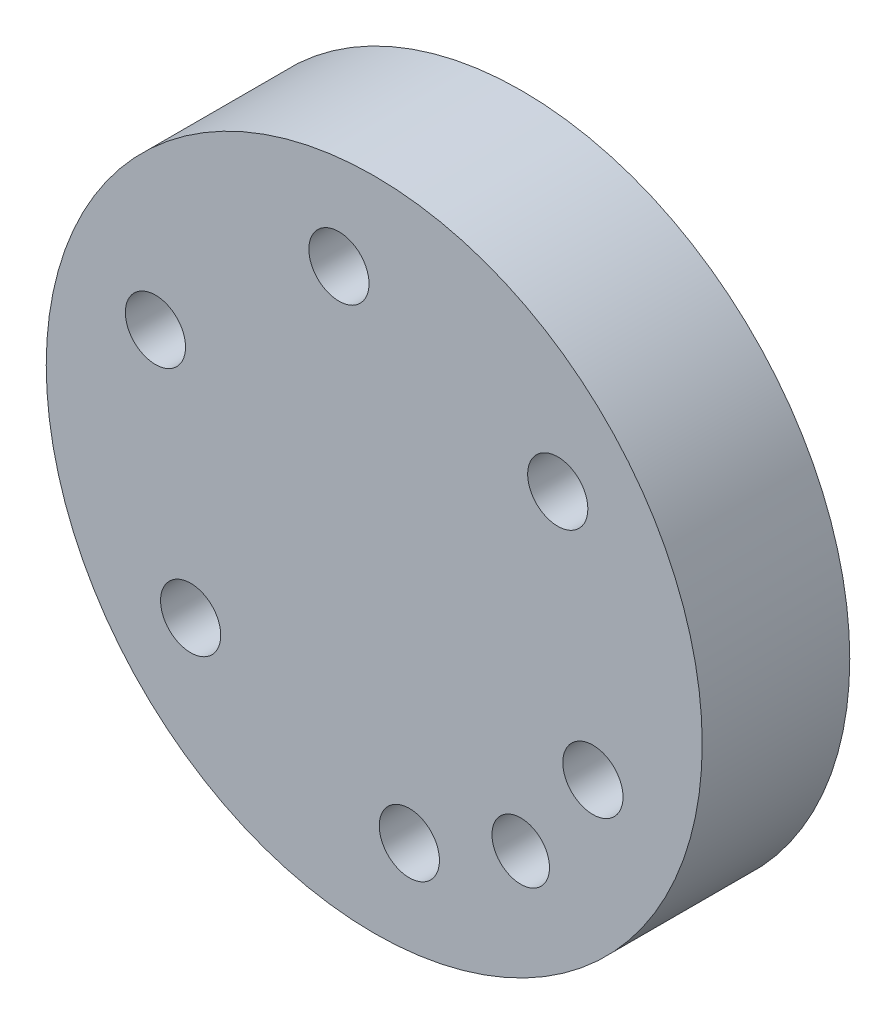
SolidWorks part; units mm, degrees
ref_plane "Front Plane" through (0, 0, 0) normal (0, 0, 1) x (1, 0, 0)
ref_plane "Top Plane" through (0, 0, 0) normal (0, 1, 0) x (1, 0, 0)
ref_plane "Right Plane" through (0, 0, 0) normal (1, 0, 0) x (0, 0, -1)
sketch "Sketch2" plane through (0, 0, 0) normal (0, 0, 1) x (1, 0, 0)
  circle A2 centre (22.3808, 278.1504) radius 88.7
  arc A4 (22.3808, 354.5504) -> (22.3808, 201.7504) centre (22.3808, 278.1504) ccw
  arc A5 (22.3808, 201.7504) -> (22.3808, 354.5504) centre (22.3808, 278.1504) ccw
  arc A6 (22.3808, 354.5504) -> (22.3808, 201.7504) centre (22.3808, 278.1504) ccw
  arc A7 (22.3808, 201.7504) -> (22.3808, 354.5504) centre (22.3808, 278.1504) ccw
  dimension "D2" = 177.4
  dimension "D1" = 0.2
extrude "Boss-Extrude1" add sketch "Sketch2" against normal blind 24.9
sketch "Sketch3" plane through (0, 0, 0) normal (0, 0, 1) x (1, 0, 0)
  circle A1 centre (22.3808, 278.1504) radius 88.7
  circle A2 centre (22.3808, 278.1504) radius 88.7
  circle A120 centre (12.8349, 340.868) radius 8.1375
  circle A121 centre (72.0102, 317.7343) radius 8.1375
  circle A122 centre (-36.7846, 301.2181) radius 8.1375
  circle A123 centre (-27.2648, 238.487) radius 8.1375
  circle A124 centre (31.8806, 215.335) radius 8.1375
  circle A125 centre (81.5193, 254.9712) radius 8.1375
  arc A126 (61.9965, 220.7534) -> (61.9965, 236.3127) centre (61.9965, 228.5331) ccw construction
  arc A127 (61.9965, 236.3127) -> (61.9965, 220.7534) centre (61.9965, 228.5331) ccw construction
  arc A128 (61.9965, 236.3127) -> (61.9965, 220.7534) centre (61.9965, 228.5331) ccw
  arc A129 (61.9965, 220.7534) -> (61.9965, 236.3127) centre (61.9965, 228.5331) ccw
  dimension "D2" = 16.275
  dimension "D1" = 0
extrude "Boss-Extrude2" add sketch "Sketch3" along normal blind 15
fillet "Fillet1" radius 2 1 edges at (69.7762, 228.5331, 0)
chamfer "Chamfer1" distance 4.5 distance2 8 1 edges at (98.7808, 278.1504, -24.9) first distance on face at (98.7808, 278.1504, -24.9)
fillet "Fillet2" radius 3 1 edges at (98.7808, 278.1504, -16.9)
fillet "Fillet3" radius 2 1 edges at (103.2808, 278.1504, -24.9)
